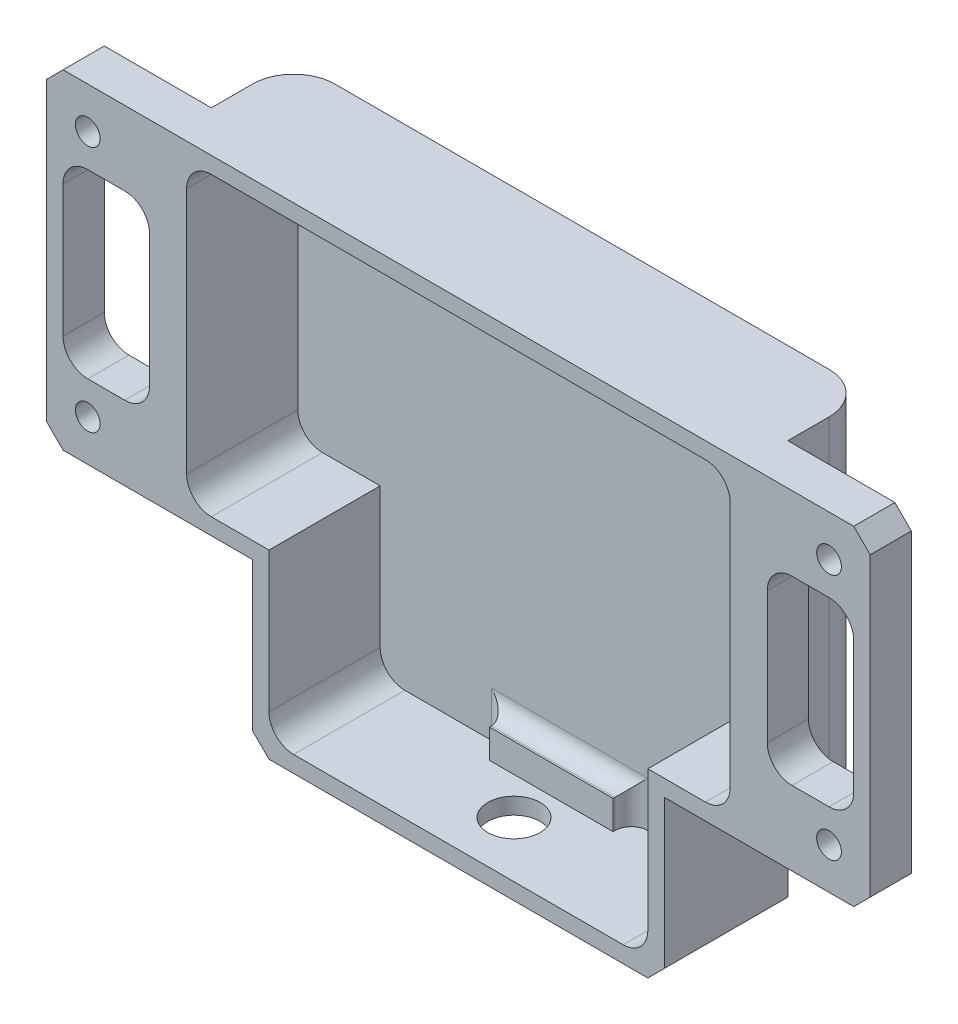
SolidWorks part; units mm, degrees
material "ABS"
ref_plane "Ebene vorne" through (0, 0, 0) normal (0, 0, 1) x (1, 0, 0)
ref_plane "Ebene oben" through (0, 0, 0) normal (0, 1, 0) x (1, 0, 0)
ref_plane "Ebene rechts" through (0, 0, 0) normal (1, 0, 0) x (0, 0, -1)
sketch "Skizze1" plane through (0, 0, 0) normal (0, 0, 1) x (1, 0, 0)
  line L0 (0, 52.8107) -> (0, -52.2189) construction
  line L1 (-65.5195, 0) -> (67.0248, 0) construction
  line L2 (-50, -20) -> (-50, 20)
  line L3 (-50, 20) -> (50, 20)
  line L4 (50, -20) -> (50, 20)
  line L5 (-50, -20) -> (-25, -20)
  line L6 (25, -20) -> (50, -20)
  line L8 (-25, -20) -> (-25, -40)
  line L9 (-25, -40) -> (25, -40)
  line L10 (25, -20) -> (25, -40)
  point P9 (0, 20)
  point P10 (0, -20)
  point P12 (50, 0)
  point P13 (-50, 0)
  point P17 (0, -40)
  dimension "D1" = 40
  dimension "D2" = 100
  dimension "D3" = 20
  dimension "D4" = 50
extrude "Aufsatz-Linear austragen1" add sketch "Skizze1" along normal blind 2.5 and the other way blind 2.5
sketch "Skizze2" plane through (0, 0, 0) normal (0, 0, 1) x (1, 0, 0)
  line L0 (0, 30.9245) -> (0, -26.0823) construction
  line L1 (-65.8109, 0) -> (54.5857, 0) construction
  circle A0 centre (-45, 15) radius 1.5
  circle A1 centre (-45, -15) radius 1.5
  circle A2 centre (45, -15) radius 1.5
  circle A3 centre (45, 15) radius 1.5
  dimension "D3" = 3
  dimension "D1" = 30
  dimension "D2" = 90
extrude "Schnitt-Linear austragen1" cut sketch "Skizze2" against normal through all and the other way through all
sketch "Skizze4" plane through (0, 0, 0) normal (0, 0, 1) x (1, 0, 0)
  line L0 (0, 35.9786) -> (0, -30.5696) construction
  line L1 (-57.4553, 0) -> (60.3332, 0) construction
  line L2 (-48, -8) -> (-48, 8)
  line L3 (-45, 11) -> (-40.5, 11)
  line L4 (-37.5, 8) -> (-37.5, -8)
  line L5 (-45, -11) -> (-40.5, -11)
  line L6 (45, -11) -> (40.5, -11)
  line L7 (37.5, 8) -> (37.5, -8)
  line L8 (45, 11) -> (40.5, 11)
  line L9 (48, -8) -> (48, 8)
  arc A0 (-37.5, -8) -> (-40.5, -11) centre (-40.5, -8) cw
  arc A1 (-45, -11) -> (-48, -8) centre (-45, -8) cw
  arc A2 (-37.5, 8) -> (-40.5, 11) centre (-40.5, 8) ccw
  arc A3 (-48, 8) -> (-45, 11) centre (-45, 8) cw
  arc A4 (48, 8) -> (45, 11) centre (45, 8) ccw
  arc A5 (37.5, 8) -> (40.5, 11) centre (40.5, 8) cw
  arc A6 (45, -11) -> (48, -8) centre (45, -8) ccw
  arc A7 (37.5, -8) -> (40.5, -11) centre (40.5, -8) ccw
  point P10 (-37.5, 0)
  point P11 (-48, 0)
  point P13 (-37.5, -11)
  point P16 (-48, -11)
  point P19 (-37.5, 11)
  point P22 (-48, 11)
  point P35 (48, 0)
  point P36 (37.5, 0)
  dimension "D4" = 3
  dimension "D1" = 22
  dimension "D2" = 48
  dimension "D3" = 37.5
extrude "Schnitt-Linear austragen2" cut sketch "Skizze4" against normal through all and the other way through all
sketch "Skizze7" plane through (0, 0, -2.5) normal (0, 0, -1) x (-1, 0, 0)
  line L0 (0, 37.0279) -> (0, -33.8129) construction
  line L1 (-65.6302, 0) -> (60.974, 0) construction
  line L2 (-35, 20) -> (-35, -20)
  line L3 (-50, 20) -> (50, 20) construction
  line L4 (-35, 20) -> (35, 20)
  line L5 (-25, -20) -> (-25, -40)
  line L6 (35, 20) -> (35, -20)
  line L7 (-35, -20) -> (35, -20)
  line L8 (-33, 18) -> (-33, -18) construction
  line L9 (-33, -18) -> (33, -18) construction
  line L10 (33, 18) -> (33, -18) construction
  line L11 (-33, 18) -> (33, 18) construction
  line L12 (-25, -40) -> (25, -40)
  line L13 (25, -40) -> (25, -20)
  point P13 (0, 20)
  point P14 (0, -20)
  point P16 (35, 0)
  point P17 (-35, 0)
  line M38 (50, 20) -> (-50, 20)
  line M40 (25, -20) -> (50, -20)
  line M42 (-25, -20) -> (-25, -40)
  line M43 (25, -40) -> (25, -20)
  line M44 (-50, -20) -> (-25, -20)
  line M46 (-25, -40) -> (25, -40)
  dimension "D2" = 70
  dimension "D1" = 2
extrude "Aufsatz-Linear austragen3" add sketch "Skizze7" along normal blind 10 contours L7 M42 M46 M43 | L7 L6 L2 M44 M40 M38 region at (0, 0, -2.5) region at (0, -30, -2.5)
sketch "Skizze8" plane through (0, 0, 2.5) normal (0, 0, 1) x (1, 0, 0)
  line L0 (0, 38.5492) -> (0, -31.5223) construction
  line L1 (-74.5556, 0) -> (52.9258, 0) construction
  line L2 (-23, -18) -> (-23, -35)
  line L3 (-20, -38) -> (20, -38)
  line L4 (23, -35) -> (23, -18)
  line L5 (-25, -20) -> (-25, -40) construction
  line L6 (-25, -40) -> (25, -40) construction
  line L14 (33, -15) -> (33, 15)
  line L15 (-30, -18) -> (30, -18)
  line L16 (-33, 15) -> (-33, -15)
  line L17 (30, 18) -> (-30, 18)
  arc A0 (30, 18) -> (33, 15) centre (30, 15) cw
  arc A1 (-30, -18) -> (-33, -15) centre (-30, -15) cw
  arc A2 (30, -18) -> (33, -15) centre (30, -15) ccw
  arc A3 (20, -38) -> (23, -35) centre (20, -35) ccw
  arc A4 (-23, -35) -> (-20, -38) centre (-20, -35) ccw
  arc A15 (-30, 18) -> (-33, 15) centre (-30, 15) ccw
  dimension "D3" = 3
  dimension "D6" = 3
  dimension "D1" = 36
  dimension "D2" = 66
  dimension "D4" = 2
  dimension "D5" = 2
extrude "Schnitt-Linear austragen6" cut sketch "Skizze8" against normal offset from surface (13.5 mm away) 1.5 contours L17 A15 L16 A1 L15 A2 L14 A0 | L2 A4 L3 A3 L4 L15 region at (0, -27.9607, 2.5) region at (0, 0, 2.5) up to face at (0, -15, -12.5)
chamfer "Fase1" distance 2 angle 45 6 edges at (-50, 20, 0) (-50, -20, 0) (50, 20, 0) (50, -20, 0) (-25, -40, -5) (25, -40, -5)
sketch "Sketch1" plane through (0, -40, 0) normal (0, 1, 0) x (1, 0, 0)
  line L0 (48, -2.5) -> (-48, -2.5) construction
  circle A0 centre (0, 4.25) radius 3.175
  dimension "D1" = 6.35
  dimension "D2" = 6.75
extrude "Cut-Extrude1" cut sketch "Sketch1" along normal blind 10
sketch "Sketch2" plane through (0, 0, -11) normal (0, 0, 1) x (1, 0, 0)
  line L1 (-7.5, -34.5) -> (7.5, -34.5)
  line L2 (-7.5, -34.5) -> (-7.5, -38)
  line L3 (-7.5, -38) -> (7.5, -38)
  line L4 (7.5, -34.5) -> (7.5, -38)
  line L5 (-20, -38) -> (20, -38) construction
  point P7 (0, -38)
  point P8 (0, 0)
  point P9 (0, 0)
  dimension "D1" = 15
  dimension "D2" = 3.5
extrude "Boss-Extrude1" add sketch "Sketch2" along normal blind 2.225
fillet "Fillet2" radius 5 2 edges at (35, 0, -12.5) (-35, 0, -12.5)
fillet "Fillet1" radius 2 3 edges at (7.5, -36.25, -11) (-7.5, -36.25, -11) (0, -34.5, -11)
